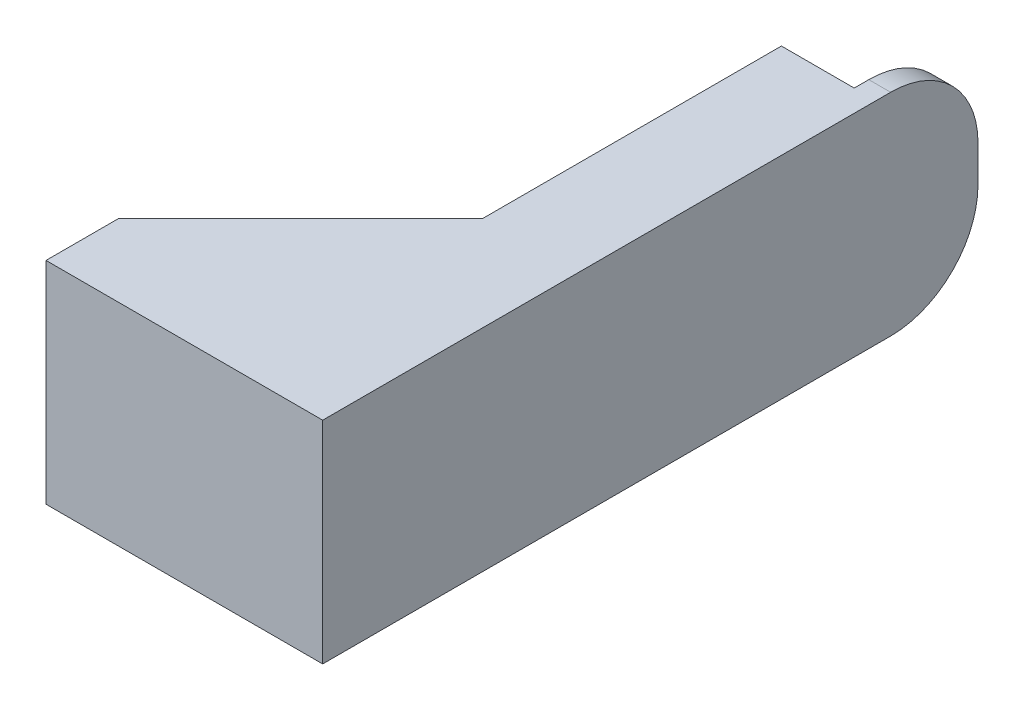
SolidWorks part; units mm, degrees
ref_plane "Front Plane" through (0, 0, 0) normal (0, 0, 1) x (1, 0, 0)
ref_plane "Top Plane" through (0, 0, 0) normal (0, 1, 0) x (1, 0, 0)
ref_plane "Right Plane" through (0, 0, 0) normal (1, 0, 0) x (0, 0, -1)
sketch "Sketch1" plane through (0, 0, 0) normal (0, 0, 1) x (1, 0, 0)
  line L0 (-38, 0) -> (0, 0) construction
  line L1 (0, -14.5) -> (-38, -14.5)
  line L2 (0, -14.5) -> (0, 14.5)
  line L3 (0, 14.5) -> (-38, 14.5)
  line L4 (-38, -14.5) -> (-38, 14.5)
  line L5 (0, 0) -> (-38, 0) construction
  dimension "D1" = 29
  dimension "D2" = 38
extrude "Boss-Extrude1" add sketch "Sketch1" against normal blind 50
sketch "Sketch2" plane through (0, 0, -50) normal (0, 0, -1) x (-1, 0, 0)
  line L0 (0, 14.5) -> (38, 14.5) construction
  line L1 (0, -14.5) -> (13, -14.5)
  line L2 (0, -14.5) -> (0, 14.5)
  line L3 (0, 14.5) -> (13, 14.5)
  line L4 (13, -14.5) -> (13, 14.5)
  dimension "D1" = 13
extrude "Boss-Extrude2" add sketch "Sketch2" along normal blind 40
chamfer "Chamfer1" distance 40 angle 45 1 edges at (-38, 0, -50)
sketch "Sketch3" plane through (0, 0, -90) normal (0, 0, -1) x (-1, 0, 0)
  line L0 (0, -14.5) -> (13, -14.5) construction
  line L1 (13, 14.5) -> (3, 14.5)
  line L2 (13, 14.5) -> (13, -14.5)
  line L3 (13, -14.5) -> (3, -14.5)
  line L4 (3, 14.5) -> (3, -14.5)
  line L5 (0, 14.5) -> (0, -14.5) construction
  dimension "D1" = 3
extrude "Cut-Extrude1" cut sketch "Sketch3" against normal blind 14
fillet "Fillet1" radius 12 2 edges at (-1.5, 14.5, -90) (-1.5, -14.5, -90)
